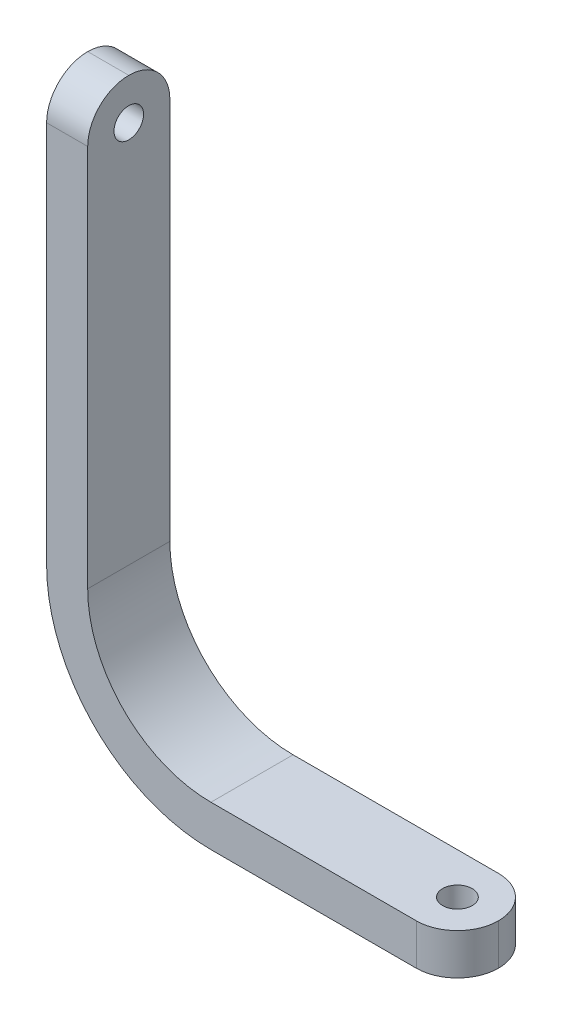
SolidWorks part; units mm, degrees
ref_plane "Front Plane" through (0, 0, 0) normal (0, 0, 1) x (1, 0, 0)
ref_plane "Top Plane" through (0, 0, 0) normal (0, 1, 0) x (1, 0, 0)
ref_plane "Right Plane" through (0, 0, 0) normal (1, 0, 0) x (0, 0, -1)
sketch "Sketch3" plane through (0, 0, 0) normal (0, 0, 1) x (1, 0, 0)
  line L0 (0, 0) -> (-30, 0)
  line L1 (-50, 20) -> (-50, 71.6274)
  line L2 (-50, 71.6274) -> (-45, 71.6274)
  line L3 (-45, 71.6274) -> (-45, 20)
  line L5 (0, 5) -> (0, 0)
  line L7 (-30, 5) -> (0, 5)
  arc A0 (-45, 20) -> (-30, 5) centre (-30, 20) ccw
  arc A1 (-50, 20) -> (-30, 0) centre (-30, 20) ccw
  dimension "D5" = 15
  dimension "D6" = 20
  dimension "D1" = 5
  dimension "D2" = 5
  dimension "D3" = 71.6274
  dimension "D4" = 50
extrude "Boss-Extrude1" add sketch "Sketch3" along normal blind 10
fillet "Fillet1" radius 5 4 edges at (0, 2.5, 10) (0, 2.5, 0) (-47.5, 71.6274, 0) (-47.5, 71.6274, 10)
sketch "Sketch4" plane through (-50, 0, 0) normal (-1, 0, 0) x (0, 0, 1)
  circle A0 centre (5, 66.6274) radius 1.7
  point P0 (5, 66.6274)
  dimension "D1" = 3.4
sketch "Sketch5" plane through (0, 0, 0) normal (0, -1, 0) x (1, 0, 0)
  circle A0 centre (-5, 5) radius 1.7
  point P0 (-5, 5)
  dimension "D1" = 3.4
hole_wizard "M3 Clearance Hole1" positions "Sketch5" profile "Sketch6" hole size "M3" standard "ANSI Metric" end condition up to next
sketch "Sketch6" plane through (-5, 0, 5) normal (1, 0, 0) x (0, 0, -1)
  line L0 (0, 0) -> (0, 5)
  line L1 (0, 5) -> (1.8, 5)
  line L2 (1.8, 5) -> (1.8, 0)
  line L5 (1.8, 0) -> (0, 0)
  line L11 (0, -6.35) -> (0, 107.95) construction
  dimension "Thru Hole Dia." = 3.6
  dimension "Thru Hole Depth" = 5
hole_wizard "M3 Clearance Hole2" positions "Sketch4" profile "Sketch7" hole size "M3" standard "ANSI Metric" end condition up to next
sketch "Sketch7" plane through (-50, 66.6274, 5) normal (0, 1, 0) x (0, 0, 1)
  line L0 (0, 0) -> (0, 5)
  line L1 (0, 5) -> (1.8, 5)
  line L2 (1.8, 5) -> (1.8, 0)
  line L5 (1.8, 0) -> (0, 0)
  line L11 (0, -6.35) -> (0, 107.95) construction
  dimension "Thru Hole Dia." = 3.6
  dimension "Thru Hole Depth" = 5
